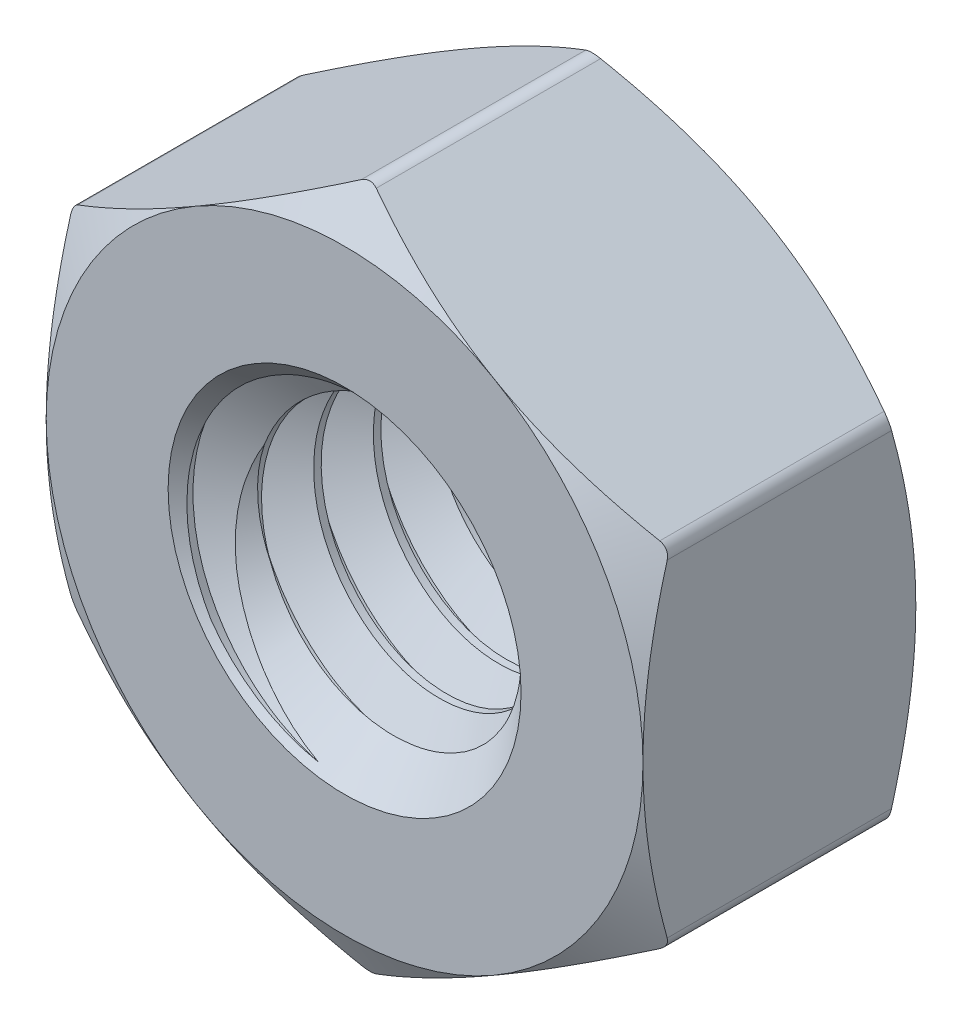
SolidWorks part; units mm, degrees
ref_plane "Front" through (0, 0, 0) normal (0, 0, 1) x (1, 0, 0)
ref_plane "Top" through (0, 0, 0) normal (0, 1, 0) x (1, 0, 0)
ref_plane "Right" through (0, 0, 0) normal (1, 0, 0) x (0, 0, -1)
sketch "Sketch1" plane through (0, 0, 0) normal (0, 0, 1) x (1, 0, 0)
  line L0 (0, 2) -> (0, 1.3) construction
  line L1 (-3.5, 2.0207) -> (-3.5, -2.0207)
  line L2 (-3.5, -2.0207) -> (0, -4.0415)
  line L3 (0, -4.0415) -> (3.5, -2.0207)
  line L4 (3.5, -2.0207) -> (3.5, 2.0207)
  line L5 (3.5, 2.0207) -> (0, 4.0415)
  line L6 (0, 4.0415) -> (-3.5, 2.0207)
  circle A0 centre (0, 0) radius 3.5 construction
  circle A1 centre (0, 0) radius 2 construction
  point P10 (0, 2)
  dimension "Width" = 7
  dimension "Thread Size" = 4
  dimension "Thread Pitch" = 0.7
sketch "Sketch2" plane through (0, 0, 0) normal (1, 0, 0) x (0, 0, -1)
  line L0 (-1.6, 0) -> (1.6, 0) construction
  line L1 (-1.6, 4.0415) -> (1.6, 4.0415) construction
  dimension "Height" = 3.2
sketch "Sketch15" plane through (0, 0, 0) normal (0, 0, 1) x (1, 0, 0)
  line L1 (0, 4.0415) -> (-3.5, 2.0207)
  line L2 (-3.5, 2.0207) -> (-3.5, -2.0207)
  line L3 (-3.5, -2.0207) -> (0, -4.0415)
  line L4 (0, -4.0415) -> (3.5, -2.0207)
  line L5 (3.5, -2.0207) -> (3.5, 2.0207)
  line L6 (3.5, 2.0207) -> (0, 4.0415)
  circle A0 centre (0, 0) radius 3.5 construction
extrude "Boss-Extrude2" add sketch "Sketch15" along normal mid plane 3.2
sketch "Sketch16" plane through (0, 0, 0) normal (0, 0, 1) x (1, 0, 0)
  circle A0 centre (0, 0) radius 2 construction
  circle A1 centre (0, 0) radius 2
sketch "Sketch4" plane through (0, 0, -1.6) normal (0, 0, -1) x (-1, 0, 0)
  circle A0 centre (0, 0) radius 2 construction
  circle A1 centre (0, 0) radius 2
extrude "Cut-Extrude4" cut sketch "Sketch16" against normal through all both and the other way through all
sketch "Sketch7" plane through (0, 0, 1.6) normal (0, 0, 1) x (1, 0, 0)
  circle A0 centre (0, 0) radius 3.5 construction
  circle A1 centre (0, 0) radius 3.5
extrude "Cut-Extrude5" cut sketch "Sketch7" against normal through all draft 60 flip side to cut
mirror "Mirror4" about plane through (0, 0, 0) normal (0, 0, 1) of "Cut-Extrude5"
fillet "Fillet2" radius 0.175 6 edges at (-3.5, 2.0207, 0) (-3.5, -2.0207, 0) (0, -4.0415, 0) (3.5, -2.0207, 0) (3.5, 2.0207, 0) (0, 4.0415, 0)
sketch "Sketch8" plane through (0, 0, 1.6) normal (0, 0, 1) x (1, 0, 0)
  line L0 (0.5176, -1.9319) -> (0, 0) construction
  line L2 (0, 2) -> (0, 1.3) construction
  circle A0 centre (0, 0) radius 2 construction
  point P0 (0.5176, -1.9319)
  dimension "D1" = 15
sketch "Sketch13" plane through (0, 0, -1.6) normal (0, 0, -1) x (-1, 0, 0)
  circle A0 centre (0, 0) radius 2 construction
  circle A1 centre (0, 0) radius 2
extrude "Boss-Extrude1" add sketch "Sketch13" against normal up to surface (3.2 mm away) separate body up to face at (2, 0, 1.6)
curve "Helix/Spiral3" pitch 0.7 height 3.2 radius 2 centre (0, 0, -1.6) axis (0, 0, 1) start towards (0, 1, 0)
sketch "Sketch12" plane through (0, 0, 0) normal (1, 0, 0) x (0, 0, -1)
  line L0 (2.2125, 2) -> (1.6, 2)
  line L1 (2.2125, 2) -> (1.95, 1.5453)
  line L2 (1.95, 1.5453) -> (1.8625, 1.5453)
  line L3 (1.8625, 1.5453) -> (1.6, 2)
  line L4 (1.9062, 1.5453) -> (1.9062, 2) construction
  line L5 (1.7313, 1.7727) -> (2.0812, 1.7727) construction
  dimension "D1" = 60
  dimension "D2" = 0.0875
  dimension "D3" = 0.35
sweep "Cut-Sweep1" cut profiles "Sketch12" path "Helix/Spiral3" align with end faces yes
sketch "Sketch17" plane through (0, 0, 1.6) normal (0, 0, 1) x (1, 0, 0)
  circle A1 centre (0, 0) radius 2
  circle A2 centre (0, 0) radius 2
  dimension "D1" = 0
extrude "Boss-Extrude3" add sketch "Sketch17" against normal up to surface (3.2 mm away) up to face at (2, 0, -1.6)
combine bodies "Combine1" operation type subtract main body 127 bodies to subtract 118
sketch "Sketch10" plane through (0, 0, 1.6) normal (0, 0, 1) x (1, 0, 0)
  circle A0 centre (0, 0) radius 2 construction
  circle A1 centre (0, 0) radius 2 construction
  circle A2 centre (0, 0) radius 2.07
  dimension "D1" = 0.07
extrude "Cut-Extrude2" cut sketch "Sketch10" against normal through all draft 45
sketch "Sketch11" plane through (0, 0, -1.6) normal (0, 0, -1) x (-1, 0, 0)
  circle A1 centre (0, 0) radius 2.07 construction
  circle A2 centre (0, 0) radius 2.07
extrude "Cut-Extrude3" cut sketch "Sketch11" against normal through all draft 45
ref_axis "Axis1" through (0, 0, -1.9933) along (0, 0, 1)
equation "\"D1\"= \"Height@Sketch2\""
equation "\"D3@Helix/Spiral3\"=\"Height@Sketch2\""
equation "\"D4@Helix/Spiral3\"=\"Thread Pitch@Sketch1\""
equation "\"D2@Sketch12\" = \"D4@Helix/Spiral3\"*.125"
equation "\"D3@Sketch12\" = \"D4@Helix/Spiral3\"*.50"
equation "\"D1@Boss-Extrude2\"=\"Height@Sketch2\""
equation "\"D1@Fillet2\"=\"Width@Sketch1\"*0.025"
equation "\"D1@Sketch10\"=\"Thread Pitch@Sketch1\"*0.1"
